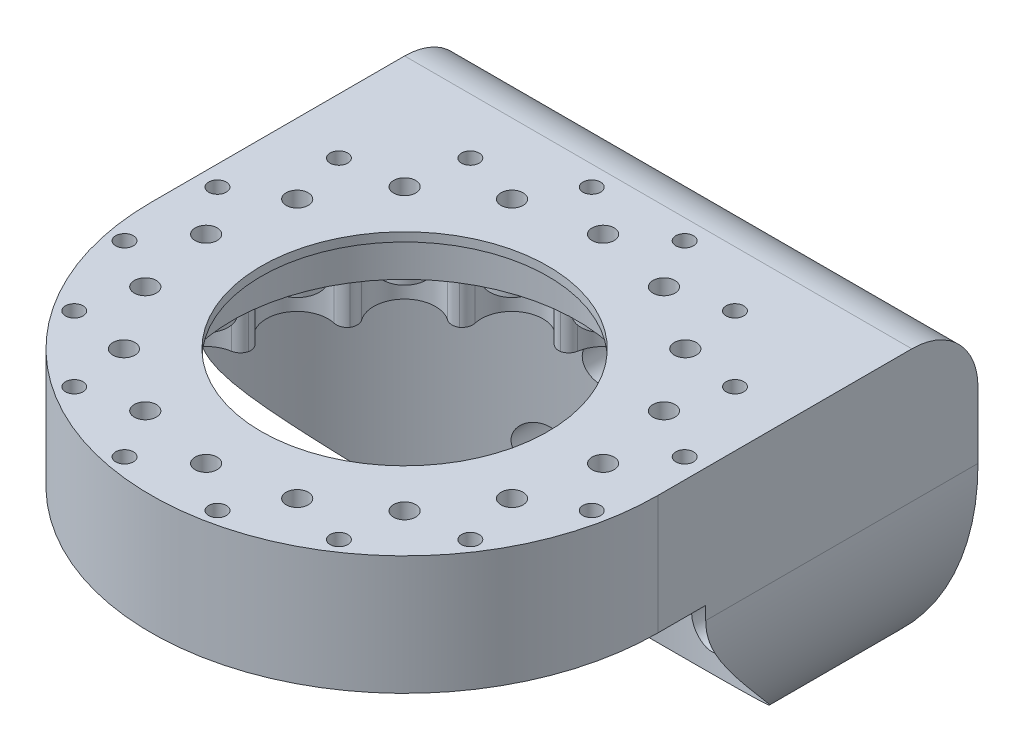
SolidWorks part; units mm, degrees
ref_plane "Front Plane" through (0, 0, 0) normal (0, 0, 1) x (1, 0, 0)
ref_plane "Top Plane" through (0, 0, 0) normal (0, 1, 0) x (1, 0, 0)
ref_plane "Right Plane" through (0, 0, 0) normal (1, 0, 0) x (0, 0, -1)
sketch "Sketch1" plane through (0, 0, 0) normal (0, 1, 0) x (1, 0, 0)
  line L0 (-10.5349, 52.9624) -> (0, 0) construction
  line L1 (0, 0) -> (24.6214, 0) construction
  circle A12 centre (0, 0) radius 39.1
  circle A13 centre (0, 0) radius 57.5
  circle A14 centre (0, 0) radius 54 construction
  circle A15 centre (-10.5349, 52.9624) radius 2
  circle A16 centre (10.5349, 52.9624) radius 2
  circle A17 centre (30.0008, 44.8994) radius 2
  circle A18 centre (44.8994, 30.0008) radius 2
  circle A19 centre (52.9624, 10.5349) radius 2
  circle A20 centre (52.9624, -10.5349) radius 2
  circle A21 centre (44.8994, -30.0008) radius 2
  circle A22 centre (30.0008, -44.8994) radius 2
  circle A23 centre (10.5349, -52.9624) radius 2
  circle A24 centre (-10.5349, -52.9624) radius 2
  circle A25 centre (-30.0008, -44.8994) radius 2
  circle A26 centre (-44.8994, -30.0008) radius 2
  circle A47 centre (-52.9624, -10.5349) radius 2
  circle A48 centre (-52.9624, 10.5349) radius 2
  circle A49 centre (-44.8994, 30.0008) radius 2
  circle A50 centre (-30.0008, 44.8994) radius 2
  point P21 (0, 0)
  point P28 (0, 0)
  point P56 (0, 0)
  point P60 (0, 0)
  dimension "D1" = 101.25
  dimension "D4" = 115
  dimension "D5" = 78.2
  dimension "D6" = 108
  dimension "D7" = 4
  dimension "D8" = 16
extrude "Boss-Extrude1" add sketch "Sketch1" along normal blind 14
sketch "Sketch2" plane through (0, 14, 0) normal (0, 1, 0) x (1, 0, 0)
  circle A0 centre (0, 0) radius 45 construction
  circle A1 centre (0, 45) radius 2.5
  circle A2 centre (17.2208, 41.5746) radius 2.5
  circle A3 centre (31.8198, 31.8198) radius 2.5
  circle A4 centre (41.5746, 17.2208) radius 2.5
  circle A5 centre (45, 0) radius 2.5
  circle A6 centre (41.5746, -17.2208) radius 2.5
  circle A7 centre (31.8198, -31.8198) radius 2.5
  circle A8 centre (17.2208, -41.5746) radius 2.5
  circle A9 centre (0, -45) radius 2.5
  circle A10 centre (-17.2208, -41.5746) radius 2.5
  circle A11 centre (-31.8198, -31.8198) radius 2.5
  circle A12 centre (-41.5746, -17.2208) radius 2.5
  circle A13 centre (-45, 0) radius 2.5
  circle A14 centre (-41.5746, 17.2208) radius 2.5
  circle A15 centre (-31.8198, 31.8198) radius 2.5
  circle A16 centre (-17.2208, 41.5746) radius 2.5
  point P27 (0, 0)
  dimension "D1" = 90
  dimension "D2" = 5
  dimension "D3" = 16
extrude "Cut-Extrude1" cut sketch "Sketch2" against normal blind 40
sketch "Sketch4" plane through (0, 0, 0) normal (0, 1, 0) x (1, 0, 0)
  circle A0 centre (0, 0) radius 45 construction
  circle A1 centre (0, 45) radius 5
  circle A2 centre (0, 45) radius 2.5
  circle A3 centre (17.2208, 41.5746) radius 2.5
  circle A4 centre (31.8198, 31.8198) radius 2.5
  circle A5 centre (41.5746, 17.2208) radius 2.5
  circle A6 centre (45, 0) radius 2.5
  circle A7 centre (41.5746, -17.2208) radius 2.5
  circle A8 centre (31.8198, -31.8198) radius 2.5
  circle A9 centre (17.2208, -41.5746) radius 2.5
  circle A10 centre (0, -45) radius 2.5
  circle A11 centre (-17.2208, -41.5746) radius 2.5
  circle A12 centre (-31.8198, -31.8198) radius 2.5
  circle A13 centre (17.2208, 41.5746) radius 5
  circle A14 centre (31.8198, 31.8198) radius 5
  circle A15 centre (41.5746, 17.2208) radius 5
  circle A16 centre (45, 0) radius 5
  circle A17 centre (41.5746, -17.2208) radius 5
  circle A18 centre (31.8198, -31.8198) radius 5
  circle A19 centre (17.2208, -41.5746) radius 5
  circle A20 centre (0, -45) radius 5
  circle A21 centre (-17.2208, -41.5746) radius 5
  circle A22 centre (-31.8198, -31.8198) radius 5
  circle A23 centre (-41.5746, -17.2208) radius 5
  circle A24 centre (-45, 0) radius 5
  circle A25 centre (-41.5746, 17.2208) radius 5
  circle A26 centre (-31.8198, 31.8198) radius 5
  circle A27 centre (-17.2208, 41.5746) radius 5
  circle A28 centre (-41.5746, -17.2208) radius 2.5
  circle A29 centre (-45, 0) radius 2.5
  circle A30 centre (-41.5746, 17.2208) radius 2.5
  circle A31 centre (-31.8198, 31.8198) radius 2.5
  circle A32 centre (-17.2208, 41.5746) radius 2.5
  point P29 (0, 0)
  point P50 (0, 0)
  dimension "D1" = 10
  dimension "D2" = 16
  dimension "D3" = 16
extrude "Boss-Extrude3" add sketch "Sketch4" against normal blind 1.8
sketch "Sketch5" plane through (0, 0, 0) normal (0, -1, 0) x (1, 0, 0)
  circle A0 centre (0, 0) radius 57.5
  circle A1 centre (0, 0) radius 45
  circle A2 centre (0, 45) radius 7
  circle A3 centre (17.2208, 41.5746) radius 7
  circle A4 centre (31.8198, 31.8198) radius 7
  circle A5 centre (41.5746, 17.2208) radius 7
  circle A6 centre (45, 0) radius 7
  circle A7 centre (41.5746, -17.2208) radius 7
  circle A8 centre (31.8198, -31.8198) radius 7
  circle A9 centre (17.2208, -41.5746) radius 7
  circle A10 centre (0, -45) radius 7
  circle A11 centre (-17.2208, -41.5746) radius 7
  circle A12 centre (-31.8198, -31.8198) radius 7
  circle A13 centre (-41.5746, -17.2208) radius 7
  circle A14 centre (-45, 0) radius 7
  circle A15 centre (-41.5746, 17.2208) radius 7
  circle A16 centre (-31.8198, 31.8198) radius 7
  circle A17 centre (-17.2208, 41.5746) radius 7
  circle A18 centre (0, 0) radius 54 construction
  circle A19 centre (-10.5349, 52.9624) radius 2
  circle A20 centre (10.5349, 52.9624) radius 2
  circle A21 centre (30.0008, 44.8994) radius 2
  circle A22 centre (44.8994, 30.0008) radius 2
  circle A23 centre (52.9624, 10.5349) radius 2
  circle A24 centre (52.9624, -10.5349) radius 2
  circle A25 centre (44.8994, -30.0008) radius 2
  circle A26 centre (30.0008, -44.8994) radius 2
  circle A27 centre (10.5349, -52.9624) radius 2
  circle A28 centre (-10.5349, -52.9624) radius 2
  circle A29 centre (-30.0008, -44.8994) radius 2
  circle A30 centre (-44.8994, -30.0008) radius 2
  circle A31 centre (-52.9624, -10.5349) radius 2
  circle A32 centre (-52.9624, 10.5349) radius 2
  circle A33 centre (-44.8994, 30.0008) radius 2
  circle A34 centre (-30.0008, 44.8994) radius 2
  point P39 (0, 0)
  point P75 (0, 0)
  circle M34 centre (0, 0) radius 57.5
  circle M35 centre (-52.9624, 10.5349) radius 2
  circle M37 centre (-52.9624, -10.5349) radius 2
  circle M39 centre (-30.0008, -44.8994) radius 2
  circle M41 centre (10.5349, -52.9624) radius 2
  circle M43 centre (44.8994, -30.0008) radius 2
  circle M45 centre (52.9624, 10.5349) radius 2
  circle M47 centre (30.0008, 44.8994) radius 2
  circle M49 centre (-10.5349, 52.9624) radius 2
  dimension "D1" = 14
  dimension "D2" = 16
  dimension "D3" = 16
extrude "Boss-Extrude4" add sketch "Sketch5" along normal blind 13 contours A17 A1 A2 A3 A4 A5 A6 A7 A8 A9 A10 A11 A12 A13 A14 A15 A16 M34 M35 M37 M39 M41 M43 M45 M47 M49 region at (-55.8737, 0, 0)
fillet "Fillet2" radius 2.5 32 edges at (-23.46, -6.5, -38.4009) (-26.5001, -6.5, -36.3696) (-6.9788, -6.5, -44.4556) (-10.5648, -6.5, -43.7422) (10.5648, -6.5, -43.7422) (6.9788, -6.5, -44.4556) (26.5001, -6.5, -36.3696) (23.46, -6.5, -38.4009) (38.4009, -6.5, -23.46) (36.3696, -6.5, -26.5001) (44.4556, -6.5, -6.9788) (43.7422, -6.5, -10.5648) (43.7422, -6.5, 10.5648) (44.4556, -6.5, 6.9788) (-38.4009, -6.5, -23.46) (-36.3696, -6.5, -26.5001) (-44.4556, -6.5, -6.9788) (-43.7422, -6.5, -10.5648) (-43.7422, -6.5, 10.5648) (-44.4556, -6.5, 6.9788) (-36.3696, -6.5, 26.5001) (-38.4009, -6.5, 23.46) (-23.46, -6.5, 38.4009) (-26.5001, -6.5, 36.3696) (-10.5648, -6.5, 43.7422) (-6.9788, -6.5, 44.4556) (6.9788, -6.5, 44.4556) (10.5648, -6.5, 43.7422) (23.46, -6.5, 38.4009) (26.5001, -6.5, 36.3696) (38.4009, -6.5, 23.46) (36.3696, -6.5, 26.5001)
sketch "Sketch6" plane through (0, -13, 0) normal (0, -1, 0) x (1, 0, 0)
  line L0 (-57.5, 0) -> (57.5, 0) construction
  line L1 (57.5, 0) -> (57.5, -57.5)
  line L2 (57.5, -57.5) -> (-57.5, -57.5)
  line L3 (-57.5, -57.5) -> (-57.5, 0)
  circle A0 centre (0, 0) radius 57.5 construction
  arc A1 (-57.5, 0) -> (57.5, 0) centre (0, 0) ccw
extrude "Boss-Extrude7" add sketch "Sketch6" against normal blind 27 contours A1 L2 L1 | A1 L3 L2 region at (-44.6563, -13, -44.6563) region at (44.6563, -13, -44.6563)
sketch "Sketch7" plane through (-57.5, 0, 0) normal (-1, 0, 0) x (0, 0, 1)
  line L0 (-57.5, 14) -> (-57.5, -73.5)
  line L1 (-57.5, -73.5) -> (-72.5, -73.5)
  line L2 (-72.5, -73.5) -> (-72.5, 14)
  line L3 (-72.5, 14) -> (-57.5, 14)
  line L4 (-57.5, -73.5) -> (0, -13)
  line L5 (0, -13) -> (-57.5, -13)
  line M5 (-57.5, -13) -> (0, -13)
  line M8 (-57.5, 14) -> (-57.5, -13)
  dimension "D1" = 15
  dimension "D2" = 87.5
  dimension "D3" = 60.5
extrude "Boss-Extrude8" add sketch "Sketch7" against normal blind 115 contours L3 L2 L1 L0 M8 | L0 L4 M5 region at (-57.5, -29.75, -65) region at (-57.5, -33.1667, -38.3333)
sketch "Sketch8" plane through (0, -73.5, 0) normal (0, -1, 0) x (1, 0, 0)
  circle A0 centre (0, 0) radius 58.5
  dimension "D1" = 117
extrude "Cut-Extrude2" cut sketch "Sketch8" against normal up to surface (60.5 mm away) up to face at (0, -13, 28.3623)
sketch "Sketch9" plane through (0, 0, -72.5) normal (0, 0, -1) x (-1, 0, 0)
  line L0 (0, 19.2611) -> (0, -105.8991) construction
  line L1 (-57.5, -73.5) -> (57.5, -73.5) construction
  circle A0 centre (0, -43.5) radius 30 construction
  circle A1 centre (0, -43.5) radius 23 construction
  circle A2 centre (23, -43.5) radius 2.25
  circle A3 centre (11.5, -63.4186) radius 2.25
  circle A4 centre (-11.5, -63.4186) radius 2.25
  circle A5 centre (-23, -43.5) radius 2.25
  circle A6 centre (-11.5, -23.5814) radius 2.25
  circle A7 centre (11.5, -23.5814) radius 2.25
  point P22 (0, -43.5)
  dimension "D1" = 60
  dimension "D2" = 46
  dimension "D3" = 4.5
  dimension "D4" = 6
extrude "Cut-Extrude3" cut sketch "Sketch9" against normal blind 67.5
sketch "Sketch10" plane through (0, 0, 0) normal (0, 0, 1) x (1, 0, 0)
  line L0 (57.5, -73.5) -> (10.7703, -73.5) construction
  circle A0 centre (0, -43.5) radius 30 construction
  circle A1 centre (0, -43.5) radius 23 construction
  circle A2 centre (23, -43.5) radius 4.5
  circle A3 centre (11.5, -63.4186) radius 4.5
  circle A4 centre (-11.5, -63.4186) radius 4.5
  circle A5 centre (-23, -43.5) radius 4.5
  circle A6 centre (-11.5, -23.5814) radius 4.5
  circle A7 centre (11.5, -23.5814) radius 4.5
  point P19 (0, -43.5)
  dimension "D1" = 60
  dimension "D2" = 46
  dimension "D3" = 9
  dimension "D4" = 6
extrude "Cut-Extrude4" cut sketch "Sketch10" against normal blind 62.5
sketch "Sketch11" plane through (0, 0, -72.5) normal (0, 0, -1) x (-1, 0, 0)
  line L0 (0, 13.9005) -> (0, -82.4311) construction
  line L1 (-57.5, -73.5) -> (57.5, -73.5) construction
  line L2 (-57.5, -16) -> (-57.5, -73.5)
  line L3 (-57.5, -73.5) -> (57.5, -73.5)
  line L4 (57.5, -73.5) -> (57.5, -20.06)
  circle A0 centre (0, -16) radius 57.5
  line M8 (57.5, -73.5) -> (57.5, 14)
  line M10 (-57.5, 14) -> (-57.5, -73.5)
  line M11 (-57.5, -73.5) -> (57.5, -73.5)
  dimension "D1" = 115
extrude "Cut-Extrude5" cut sketch "Sketch11" against normal blind 133 contours A0 M10 M11 | A0 L3 M8 region at (44.6563, -60.6563, -72.5) region at (-44.6563, -60.6563, -72.5)
fillet "Fillet4" radius 15 1 edges at (0, 14, -72.5)
sketch "Sketch12" plane through (0, 14, 0) normal (0, 1, 0) x (1, 0, 0)
  circle A0 centre (0, 0) radius 39.1
  circle A1 centre (0, 0) radius 32.5
  dimension "D1" = 65
extrude "Boss-Extrude9" add sketch "Sketch12" against normal blind 2
